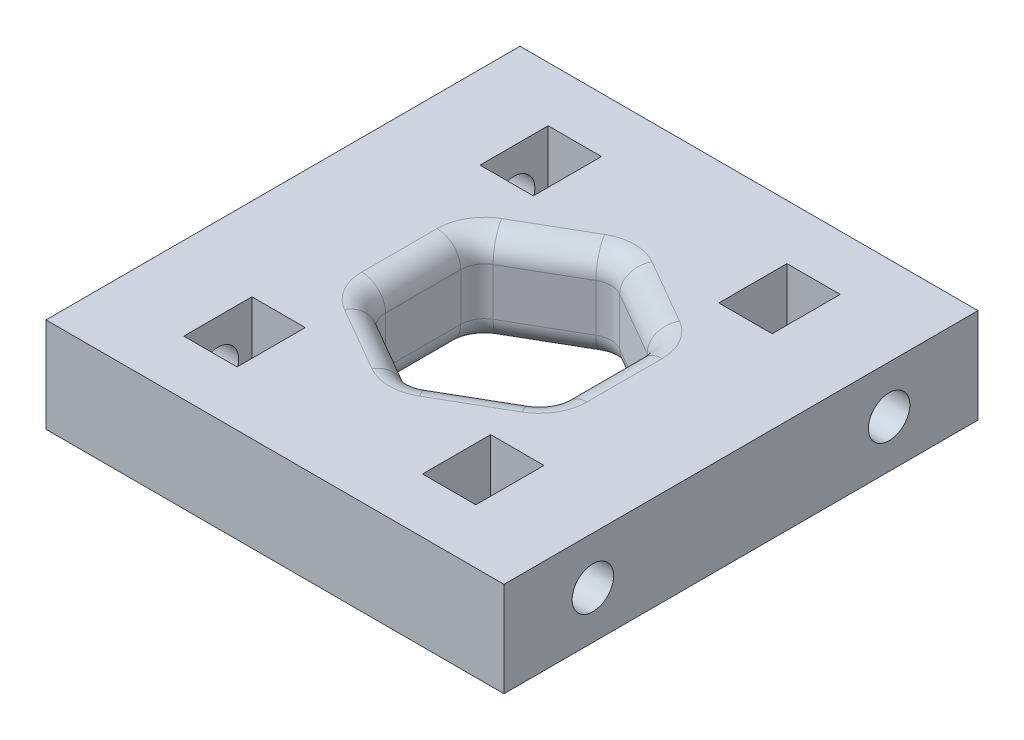
SolidWorks part; units mm, degrees
ref_plane "Front Plane" through (0, 0, 0) normal (0, 0, 1) x (1, 0, 0)
ref_plane "Top Plane" through (0, 0, 0) normal (0, 1, 0) x (1, 0, 0)
ref_plane "Right Plane" through (0, 0, 0) normal (1, 0, 0) x (0, 0, -1)
sketch "Sketch1" plane through (0, 0, 0) normal (1, 0, 0) x (0, 0, -1)
  line L1 (-20, 4) -> (20, 4)
  line L2 (-20, 4) -> (-20, -4)
  line L3 (-20, -4) -> (20, -4)
  line L4 (20, 4) -> (20, -4)
  line L5 (-20, 4) -> (20, -4) construction
  line L6 (-20, -4) -> (20, 4) construction
  point P0 (0, 0)
  dimension "D1" = 40
  dimension "D2" = 8
extrude "Boss-Extrude1" add sketch "Sketch1" along normal mid plane 38.65
sketch "Sketch2" plane through (19.325, 0, 0) normal (1, 0, 0) x (0, 0, -1)
  line L0 (0, 4) -> (0, -4) construction
  line L1 (20, 4) -> (-20, 4) construction
  line L2 (-20, -4) -> (20, -4) construction
  line L3 (-20, 0) -> (20, 0) construction
  line L4 (-20, 4) -> (-20, -4) construction
  line L5 (20, -4) -> (20, 4) construction
  circle A0 centre (-12.5, 0) radius 1.75
  circle A1 centre (12.5, 0) radius 1.75
  dimension "D2" = 3.5
  dimension "D1" = 25
extrude "Cut-Extrude1" cut sketch "Sketch2" against normal blind 7
ref_plane "Plane1" through (12.325, 0, 0) normal (1, 0, 0) x (0, 0, -1)
sketch "Sketch3" plane through (12.325, 0, 0) normal (1, 0, 0) x (0, 0, -1)
  line L0 (-15.375, 1.6599) -> (-15.375, 4)
  line L1 (-15.375, -1.6599) -> (-12.5, -3.3198)
  line L2 (-12.5, -3.3198) -> (-9.625, -1.6599)
  line L3 (-9.625, -1.6599) -> (-9.625, 1.6599)
  line L4 (-9.625, 1.6599) -> (-12.5, 3.3198)
  line L5 (-12.5, 3.3198) -> (-15.375, 1.6599)
  line L6 (-15.375, 1.6599) -> (-15.375, -1.6599)
  line L7 (20, 4) -> (-20, 4) construction
  line L8 (-15.375, 4) -> (-9.625, 4)
  line L9 (-9.625, 4) -> (-9.625, 1.6599)
  line L10 (0, 4) -> (0, -4) construction
  line L11 (-20, -4) -> (20, -4) construction
  line L12 (9.625, 4) -> (9.625, 1.6599)
  line L13 (15.375, 4) -> (9.625, 4)
  line L14 (15.375, 1.6599) -> (15.375, 4)
  line L15 (9.625, -1.6599) -> (9.625, 1.6599)
  line L16 (12.5, -3.3198) -> (9.625, -1.6599)
  line L17 (15.375, -1.6599) -> (12.5, -3.3198)
  line L18 (15.375, 1.6599) -> (15.375, -1.6599)
  circle A0 centre (-12.5, 0) radius 2.875 construction
  dimension "D1" = 5.75
extrude "Cut-Extrude2" cut sketch "Sketch3" against normal blind 4.5 contours L5 L6 L1 L2 L3 L4 | L9 L8 L0 L5 L4 | L18 L14 L13 L12 L15 L16 L17 region at (12.325, 2.8299, 15.3129) region at (12.325, 0, 12.5) region at (12.325, 0.7374, -12.5)
mirror "Mirror1" about plane through (0, 0, 0) normal (1, 0, 0) of "Cut-Extrude2", "Cut-Extrude1"
sketch "Sketch4" plane through (0, 4, 0) normal (0, 1, 0) x (1, 0, 0)
  line L1 (0, -8.6603) -> (7.5, -4.3301)
  line L2 (7.5, -4.3301) -> (7.5, 4.3301)
  line L3 (7.5, 4.3301) -> (0, 8.6603)
  line L4 (0, 8.6603) -> (-7.5, 4.3301)
  line L5 (-7.5, 4.3301) -> (-7.5, -4.3301)
  line L6 (-7.5, -4.3301) -> (0, -8.6603)
  circle A0 centre (0, 0) radius 7.5 construction
  dimension "D1" = 15
extrude "Cut-Extrude3" cut sketch "Sketch4" against normal up to next
fillet "Fillet1" radius 2 18 edges at (7.5, 4, 0) (7.5, -4, 0) (7.5, 0, 4.3301) (3.75, 4, 6.4952) (3.75, -4, 6.4952) (0, 0, 8.6603) (-3.75, 4, 6.4952) (-3.75, -4, 6.4952) (-7.5, 0, 4.3301) (-7.5, 4, 0) (-7.5, -4, 0) (-7.5, 0, -4.3301) (-3.75, 4, -6.4952) (-3.75, -4, -6.4952) (0, 0, -8.6603) (3.75, 4, -6.4952) (7.5, 0, -4.3301) (3.75, -4, -6.4952)
